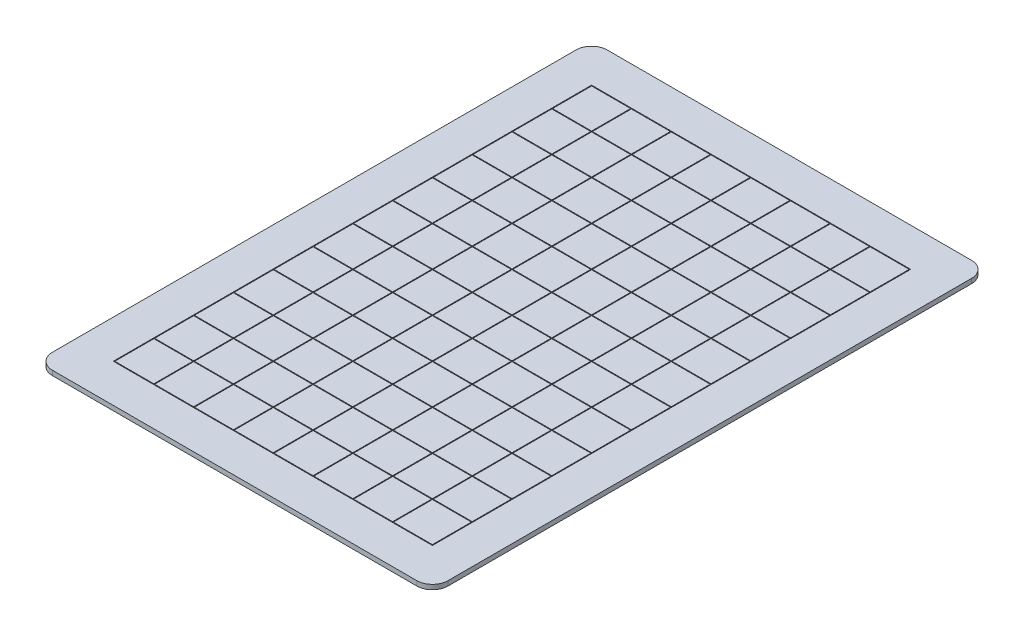
SolidWorks part; units mm, degrees
ref_plane "Front Plane" through (0, 0, 0) normal (0, 0, 1) x (1, 0, 0)
ref_plane "Top Plane" through (0, 0, 0) normal (0, 1, 0) x (1, 0, 0)
ref_plane "Right Plane" through (0, 0, 0) normal (1, 0, 0) x (0, 0, -1)
sketch "Sketch1" plane through (0, 0, 0) normal (0, 1, 0) x (1, 0, 0)
  line L1 (0, 0) -> (253.5, 0)
  line L2 (0, 0) -> (0, 355.5)
  line L3 (0, 355.5) -> (253.5, 355.5)
  line L4 (253.5, 0) -> (253.5, 355.5)
  dimension "D1" = 253.5
  dimension "D2" = 355.5
extrude "Boss-Extrude1" add sketch "Sketch1" along normal blind 3
sketch "Sketch2" plane through (0, 3, 0) normal (0, 1, 0) x (1, 0, 0)
  line L0 (0, 0) -> (253.5, 0) construction
  line L1 (25, 50) -> (50, 50)
  line L2 (25, 50) -> (25, 25)
  line L3 (25, 25) -> (50, 25)
  line L4 (50, 50) -> (50, 25)
  line L5 (0, 355.5) -> (0, 0) construction
  line L6 (50.5, 50) -> (50.5, 25)
  line L7 (50.5, 50) -> (75.5, 50)
  line L8 (75.5, 50) -> (75.5, 25)
  line L9 (50.5, 25) -> (75.5, 25)
  line L10 (76, 50) -> (76, 25)
  line L11 (76, 50) -> (101, 50)
  line L12 (101, 50) -> (101, 25)
  line L13 (76, 25) -> (101, 25)
  line L14 (101.5, 50) -> (101.5, 25)
  line L15 (101.5, 50) -> (126.5, 50)
  line L16 (126.5, 50) -> (126.5, 25)
  line L17 (101.5, 25) -> (126.5, 25)
  line L18 (127, 50) -> (127, 25)
  line L19 (127, 50) -> (152, 50)
  line L20 (152, 50) -> (152, 25)
  line L21 (127, 25) -> (152, 25)
  line L22 (152.5, 50) -> (152.5, 25)
  line L23 (152.5, 50) -> (177.5, 50)
  line L24 (177.5, 50) -> (177.5, 25)
  line L25 (152.5, 25) -> (177.5, 25)
  line L26 (178, 50) -> (178, 25)
  line L27 (178, 50) -> (203, 50)
  line L28 (203, 50) -> (203, 25)
  line L29 (178, 25) -> (203, 25)
  line L30 (203.5, 50) -> (203.5, 25)
  line L31 (203.5, 50) -> (228.5, 50)
  line L32 (228.5, 50) -> (228.5, 25)
  line L33 (203.5, 25) -> (228.5, 25)
  line L34 (50.5, 75.5) -> (50.5, 50.5)
  line L35 (50.5, 75.5) -> (75.5, 75.5)
  line L36 (75.5, 75.5) -> (75.5, 50.5)
  line L37 (50.5, 50.5) -> (75.5, 50.5)
  line L38 (76, 75.5) -> (76, 50.5)
  line L39 (76, 75.5) -> (101, 75.5)
  line L40 (101, 75.5) -> (101, 50.5)
  line L41 (76, 50.5) -> (101, 50.5)
  line L42 (101.5, 75.5) -> (101.5, 50.5)
  line L43 (101.5, 75.5) -> (126.5, 75.5)
  line L44 (126.5, 75.5) -> (126.5, 50.5)
  line L45 (101.5, 50.5) -> (126.5, 50.5)
  line L46 (127, 75.5) -> (127, 50.5)
  line L47 (127, 75.5) -> (152, 75.5)
  line L48 (152, 75.5) -> (152, 50.5)
  line L49 (127, 50.5) -> (152, 50.5)
  line L50 (152.5, 75.5) -> (152.5, 50.5)
  line L51 (152.5, 75.5) -> (177.5, 75.5)
  line L52 (177.5, 75.5) -> (177.5, 50.5)
  line L53 (152.5, 50.5) -> (177.5, 50.5)
  line L54 (178, 75.5) -> (178, 50.5)
  line L55 (178, 75.5) -> (203, 75.5)
  line L56 (203, 75.5) -> (203, 50.5)
  line L57 (178, 50.5) -> (203, 50.5)
  line L58 (203.5, 75.5) -> (203.5, 50.5)
  line L59 (203.5, 75.5) -> (228.5, 75.5)
  line L60 (228.5, 75.5) -> (228.5, 50.5)
  line L61 (203.5, 50.5) -> (228.5, 50.5)
  line L62 (50.5, 101) -> (50.5, 76)
  line L63 (50.5, 101) -> (75.5, 101)
  line L64 (75.5, 101) -> (75.5, 76)
  line L65 (50.5, 76) -> (75.5, 76)
  line L66 (76, 101) -> (76, 76)
  line L67 (76, 101) -> (101, 101)
  line L68 (101, 101) -> (101, 76)
  line L69 (76, 76) -> (101, 76)
  line L70 (101.5, 101) -> (101.5, 76)
  line L71 (101.5, 101) -> (126.5, 101)
  line L72 (126.5, 101) -> (126.5, 76)
  line L73 (101.5, 76) -> (126.5, 76)
  line L74 (127, 101) -> (127, 76)
  line L75 (127, 101) -> (152, 101)
  line L76 (152, 101) -> (152, 76)
  line L77 (127, 76) -> (152, 76)
  line L78 (152.5, 101) -> (152.5, 76)
  line L79 (152.5, 101) -> (177.5, 101)
  line L80 (177.5, 101) -> (177.5, 76)
  line L81 (152.5, 76) -> (177.5, 76)
  line L82 (178, 101) -> (178, 76)
  line L83 (178, 101) -> (203, 101)
  line L84 (203, 101) -> (203, 76)
  line L85 (178, 76) -> (203, 76)
  line L86 (203.5, 101) -> (203.5, 76)
  line L87 (203.5, 101) -> (228.5, 101)
  line L88 (228.5, 101) -> (228.5, 76)
  line L89 (203.5, 76) -> (228.5, 76)
  line L90 (50.5, 126.5) -> (50.5, 101.5)
  line L91 (50.5, 126.5) -> (75.5, 126.5)
  line L92 (75.5, 126.5) -> (75.5, 101.5)
  line L93 (50.5, 101.5) -> (75.5, 101.5)
  line L94 (76, 126.5) -> (76, 101.5)
  line L95 (76, 126.5) -> (101, 126.5)
  line L96 (101, 126.5) -> (101, 101.5)
  line L97 (76, 101.5) -> (101, 101.5)
  line L98 (101.5, 126.5) -> (101.5, 101.5)
  line L99 (101.5, 126.5) -> (126.5, 126.5)
  line L100 (126.5, 126.5) -> (126.5, 101.5)
  line L101 (101.5, 101.5) -> (126.5, 101.5)
  line L102 (127, 126.5) -> (127, 101.5)
  line L103 (127, 126.5) -> (152, 126.5)
  line L104 (152, 126.5) -> (152, 101.5)
  line L105 (127, 101.5) -> (152, 101.5)
  line L106 (152.5, 126.5) -> (152.5, 101.5)
  line L107 (152.5, 126.5) -> (177.5, 126.5)
  line L108 (177.5, 126.5) -> (177.5, 101.5)
  line L109 (152.5, 101.5) -> (177.5, 101.5)
  line L110 (178, 126.5) -> (178, 101.5)
  line L111 (178, 126.5) -> (203, 126.5)
  line L112 (203, 126.5) -> (203, 101.5)
  line L113 (178, 101.5) -> (203, 101.5)
  line L114 (203.5, 126.5) -> (203.5, 101.5)
  line L115 (203.5, 126.5) -> (228.5, 126.5)
  line L116 (228.5, 126.5) -> (228.5, 101.5)
  line L117 (203.5, 101.5) -> (228.5, 101.5)
  line L118 (50.5, 152) -> (50.5, 127)
  line L119 (50.5, 152) -> (75.5, 152)
  line L120 (75.5, 152) -> (75.5, 127)
  line L121 (50.5, 127) -> (75.5, 127)
  line L122 (76, 152) -> (76, 127)
  line L123 (76, 152) -> (101, 152)
  line L124 (101, 152) -> (101, 127)
  line L125 (76, 127) -> (101, 127)
  line L126 (101.5, 152) -> (101.5, 127)
  line L127 (101.5, 152) -> (126.5, 152)
  line L128 (126.5, 152) -> (126.5, 127)
  line L129 (101.5, 127) -> (126.5, 127)
  line L130 (127, 152) -> (127, 127)
  line L131 (127, 152) -> (152, 152)
  line L132 (152, 152) -> (152, 127)
  line L133 (127, 127) -> (152, 127)
  line L134 (152.5, 152) -> (152.5, 127)
  line L135 (152.5, 152) -> (177.5, 152)
  line L136 (177.5, 152) -> (177.5, 127)
  line L137 (152.5, 127) -> (177.5, 127)
  line L138 (178, 152) -> (178, 127)
  line L139 (178, 152) -> (203, 152)
  line L140 (203, 152) -> (203, 127)
  line L141 (178, 127) -> (203, 127)
  line L142 (203.5, 152) -> (203.5, 127)
  line L143 (203.5, 152) -> (228.5, 152)
  line L144 (228.5, 152) -> (228.5, 127)
  line L145 (203.5, 127) -> (228.5, 127)
  line L146 (50.5, 177.5) -> (50.5, 152.5)
  line L147 (50.5, 177.5) -> (75.5, 177.5)
  line L148 (75.5, 177.5) -> (75.5, 152.5)
  line L149 (50.5, 152.5) -> (75.5, 152.5)
  line L150 (76, 177.5) -> (76, 152.5)
  line L151 (76, 177.5) -> (101, 177.5)
  line L152 (101, 177.5) -> (101, 152.5)
  line L153 (76, 152.5) -> (101, 152.5)
  line L154 (101.5, 177.5) -> (101.5, 152.5)
  line L155 (101.5, 177.5) -> (126.5, 177.5)
  line L156 (126.5, 177.5) -> (126.5, 152.5)
  line L157 (101.5, 152.5) -> (126.5, 152.5)
  line L158 (127, 177.5) -> (127, 152.5)
  line L159 (127, 177.5) -> (152, 177.5)
  line L160 (152, 177.5) -> (152, 152.5)
  line L161 (127, 152.5) -> (152, 152.5)
  line L162 (152.5, 177.5) -> (152.5, 152.5)
  line L163 (152.5, 177.5) -> (177.5, 177.5)
  line L164 (177.5, 177.5) -> (177.5, 152.5)
  line L165 (152.5, 152.5) -> (177.5, 152.5)
  line L166 (178, 177.5) -> (178, 152.5)
  line L167 (178, 177.5) -> (203, 177.5)
  line L168 (203, 177.5) -> (203, 152.5)
  line L169 (178, 152.5) -> (203, 152.5)
  line L170 (203.5, 177.5) -> (203.5, 152.5)
  line L171 (203.5, 177.5) -> (228.5, 177.5)
  line L172 (228.5, 177.5) -> (228.5, 152.5)
  line L173 (203.5, 152.5) -> (228.5, 152.5)
  line L174 (50.5, 203) -> (50.5, 178)
  line L175 (50.5, 203) -> (75.5, 203)
  line L176 (75.5, 203) -> (75.5, 178)
  line L177 (50.5, 178) -> (75.5, 178)
  line L178 (76, 203) -> (76, 178)
  line L179 (76, 203) -> (101, 203)
  line L180 (101, 203) -> (101, 178)
  line L181 (76, 178) -> (101, 178)
  line L182 (101.5, 203) -> (101.5, 178)
  line L183 (101.5, 203) -> (126.5, 203)
  line L184 (126.5, 203) -> (126.5, 178)
  line L185 (101.5, 178) -> (126.5, 178)
  line L186 (127, 203) -> (127, 178)
  line L187 (127, 203) -> (152, 203)
  line L188 (152, 203) -> (152, 178)
  line L189 (127, 178) -> (152, 178)
  line L190 (152.5, 203) -> (152.5, 178)
  line L191 (152.5, 203) -> (177.5, 203)
  line L192 (177.5, 203) -> (177.5, 178)
  line L193 (152.5, 178) -> (177.5, 178)
  line L194 (178, 203) -> (178, 178)
  line L195 (178, 203) -> (203, 203)
  line L196 (203, 203) -> (203, 178)
  line L197 (178, 178) -> (203, 178)
  line L198 (203.5, 203) -> (203.5, 178)
  line L199 (203.5, 203) -> (228.5, 203)
  line L200 (228.5, 203) -> (228.5, 178)
  line L201 (203.5, 178) -> (228.5, 178)
  line L202 (50.5, 228.5) -> (50.5, 203.5)
  line L203 (50.5, 228.5) -> (75.5, 228.5)
  line L204 (75.5, 228.5) -> (75.5, 203.5)
  line L205 (50.5, 203.5) -> (75.5, 203.5)
  line L206 (76, 228.5) -> (76, 203.5)
  line L207 (76, 228.5) -> (101, 228.5)
  line L208 (101, 228.5) -> (101, 203.5)
  line L209 (76, 203.5) -> (101, 203.5)
  line L210 (101.5, 228.5) -> (101.5, 203.5)
  line L211 (101.5, 228.5) -> (126.5, 228.5)
  line L212 (126.5, 228.5) -> (126.5, 203.5)
  line L213 (101.5, 203.5) -> (126.5, 203.5)
  line L214 (127, 228.5) -> (127, 203.5)
  line L215 (127, 228.5) -> (152, 228.5)
  line L216 (152, 228.5) -> (152, 203.5)
  line L217 (127, 203.5) -> (152, 203.5)
  line L218 (152.5, 228.5) -> (152.5, 203.5)
  line L219 (152.5, 228.5) -> (177.5, 228.5)
  line L220 (177.5, 228.5) -> (177.5, 203.5)
  line L221 (152.5, 203.5) -> (177.5, 203.5)
  line L222 (178, 228.5) -> (178, 203.5)
  line L223 (178, 228.5) -> (203, 228.5)
  line L224 (203, 228.5) -> (203, 203.5)
  line L225 (178, 203.5) -> (203, 203.5)
  line L226 (203.5, 228.5) -> (203.5, 203.5)
  line L227 (203.5, 228.5) -> (228.5, 228.5)
  line L228 (228.5, 228.5) -> (228.5, 203.5)
  line L229 (203.5, 203.5) -> (228.5, 203.5)
  line L230 (50.5, 254) -> (50.5, 229)
  line L231 (50.5, 254) -> (75.5, 254)
  line L232 (75.5, 254) -> (75.5, 229)
  line L233 (50.5, 229) -> (75.5, 229)
  line L234 (76, 254) -> (76, 229)
  line L235 (76, 254) -> (101, 254)
  line L236 (101, 254) -> (101, 229)
  line L237 (76, 229) -> (101, 229)
  line L238 (101.5, 254) -> (101.5, 229)
  line L239 (101.5, 254) -> (126.5, 254)
  line L240 (126.5, 254) -> (126.5, 229)
  line L241 (101.5, 229) -> (126.5, 229)
  line L242 (127, 254) -> (127, 229)
  line L243 (127, 254) -> (152, 254)
  line L244 (152, 254) -> (152, 229)
  line L245 (127, 229) -> (152, 229)
  line L246 (152.5, 254) -> (152.5, 229)
  line L247 (152.5, 254) -> (177.5, 254)
  line L248 (177.5, 254) -> (177.5, 229)
  line L249 (152.5, 229) -> (177.5, 229)
  line L250 (178, 254) -> (178, 229)
  line L251 (178, 254) -> (203, 254)
  line L252 (203, 254) -> (203, 229)
  line L253 (178, 229) -> (203, 229)
  line L254 (203.5, 254) -> (203.5, 229)
  line L255 (203.5, 254) -> (228.5, 254)
  line L256 (228.5, 254) -> (228.5, 229)
  line L257 (203.5, 229) -> (228.5, 229)
  line L258 (50.5, 279.5) -> (50.5, 254.5)
  line L259 (50.5, 279.5) -> (75.5, 279.5)
  line L260 (75.5, 279.5) -> (75.5, 254.5)
  line L261 (50.5, 254.5) -> (75.5, 254.5)
  line L262 (76, 279.5) -> (76, 254.5)
  line L263 (76, 279.5) -> (101, 279.5)
  line L264 (101, 279.5) -> (101, 254.5)
  line L265 (76, 254.5) -> (101, 254.5)
  line L266 (101.5, 279.5) -> (101.5, 254.5)
  line L267 (101.5, 279.5) -> (126.5, 279.5)
  line L268 (126.5, 279.5) -> (126.5, 254.5)
  line L269 (101.5, 254.5) -> (126.5, 254.5)
  line L270 (127, 279.5) -> (127, 254.5)
  line L271 (127, 279.5) -> (152, 279.5)
  line L272 (152, 279.5) -> (152, 254.5)
  line L273 (127, 254.5) -> (152, 254.5)
  line L274 (152.5, 279.5) -> (152.5, 254.5)
  line L275 (152.5, 279.5) -> (177.5, 279.5)
  line L276 (177.5, 279.5) -> (177.5, 254.5)
  line L277 (152.5, 254.5) -> (177.5, 254.5)
  line L278 (178, 279.5) -> (178, 254.5)
  line L279 (178, 279.5) -> (203, 279.5)
  line L280 (203, 279.5) -> (203, 254.5)
  line L281 (178, 254.5) -> (203, 254.5)
  line L282 (203.5, 279.5) -> (203.5, 254.5)
  line L283 (203.5, 279.5) -> (228.5, 279.5)
  line L284 (228.5, 279.5) -> (228.5, 254.5)
  line L285 (203.5, 254.5) -> (228.5, 254.5)
  line L286 (50.5, 305) -> (50.5, 280)
  line L287 (50.5, 305) -> (75.5, 305)
  line L288 (75.5, 305) -> (75.5, 280)
  line L289 (50.5, 280) -> (75.5, 280)
  line L290 (76, 305) -> (76, 280)
  line L291 (76, 305) -> (101, 305)
  line L292 (101, 305) -> (101, 280)
  line L293 (76, 280) -> (101, 280)
  line L294 (101.5, 305) -> (101.5, 280)
  line L295 (101.5, 305) -> (126.5, 305)
  line L296 (126.5, 305) -> (126.5, 280)
  line L297 (101.5, 280) -> (126.5, 280)
  line L298 (127, 305) -> (127, 280)
  line L299 (127, 305) -> (152, 305)
  line L300 (152, 305) -> (152, 280)
  line L301 (127, 280) -> (152, 280)
  line L302 (152.5, 305) -> (152.5, 280)
  line L303 (152.5, 305) -> (177.5, 305)
  line L304 (177.5, 305) -> (177.5, 280)
  line L305 (152.5, 280) -> (177.5, 280)
  line L306 (178, 305) -> (178, 280)
  line L307 (178, 305) -> (203, 305)
  line L308 (203, 305) -> (203, 280)
  line L309 (178, 280) -> (203, 280)
  line L310 (203.5, 305) -> (203.5, 280)
  line L311 (203.5, 305) -> (228.5, 305)
  line L312 (228.5, 305) -> (228.5, 280)
  line L313 (203.5, 280) -> (228.5, 280)
  line L314 (50.5, 330.5) -> (50.5, 305.5)
  line L315 (50.5, 330.5) -> (75.5, 330.5)
  line L316 (75.5, 330.5) -> (75.5, 305.5)
  line L317 (50.5, 305.5) -> (75.5, 305.5)
  line L318 (76, 330.5) -> (76, 305.5)
  line L319 (76, 330.5) -> (101, 330.5)
  line L320 (101, 330.5) -> (101, 305.5)
  line L321 (76, 305.5) -> (101, 305.5)
  line L322 (101.5, 330.5) -> (101.5, 305.5)
  line L323 (101.5, 330.5) -> (126.5, 330.5)
  line L324 (126.5, 330.5) -> (126.5, 305.5)
  line L325 (101.5, 305.5) -> (126.5, 305.5)
  line L326 (127, 330.5) -> (127, 305.5)
  line L327 (127, 330.5) -> (152, 330.5)
  line L328 (152, 330.5) -> (152, 305.5)
  line L329 (127, 305.5) -> (152, 305.5)
  line L330 (152.5, 330.5) -> (152.5, 305.5)
  line L331 (152.5, 330.5) -> (177.5, 330.5)
  line L332 (177.5, 330.5) -> (177.5, 305.5)
  line L333 (152.5, 305.5) -> (177.5, 305.5)
  line L334 (178, 330.5) -> (178, 305.5)
  line L335 (178, 330.5) -> (203, 330.5)
  line L336 (203, 330.5) -> (203, 305.5)
  line L337 (178, 305.5) -> (203, 305.5)
  line L338 (203.5, 330.5) -> (203.5, 305.5)
  line L339 (203.5, 330.5) -> (228.5, 330.5)
  line L340 (228.5, 330.5) -> (228.5, 305.5)
  line L341 (203.5, 305.5) -> (228.5, 305.5)
  line L342 (25, 75.5) -> (25, 50.5)
  line L343 (25, 75.5) -> (50, 75.5)
  line L344 (50, 75.5) -> (50, 50.5)
  line L345 (25, 50.5) -> (50, 50.5)
  line L346 (25, 101) -> (25, 76)
  line L347 (25, 101) -> (50, 101)
  line L348 (50, 101) -> (50, 76)
  line L349 (25, 76) -> (50, 76)
  line L350 (25, 126.5) -> (25, 101.5)
  line L351 (25, 126.5) -> (50, 126.5)
  line L352 (50, 126.5) -> (50, 101.5)
  line L353 (25, 101.5) -> (50, 101.5)
  line L354 (25, 152) -> (25, 127)
  line L355 (25, 152) -> (50, 152)
  line L356 (50, 152) -> (50, 127)
  line L357 (25, 127) -> (50, 127)
  line L358 (25, 177.5) -> (25, 152.5)
  line L359 (25, 177.5) -> (50, 177.5)
  line L360 (50, 177.5) -> (50, 152.5)
  line L361 (25, 152.5) -> (50, 152.5)
  line L362 (25, 203) -> (25, 178)
  line L363 (25, 203) -> (50, 203)
  line L364 (50, 203) -> (50, 178)
  line L365 (25, 178) -> (50, 178)
  line L366 (25, 228.5) -> (25, 203.5)
  line L367 (25, 228.5) -> (50, 228.5)
  line L368 (50, 228.5) -> (50, 203.5)
  line L369 (25, 203.5) -> (50, 203.5)
  line L370 (25, 254) -> (25, 229)
  line L371 (25, 254) -> (50, 254)
  line L372 (50, 254) -> (50, 229)
  line L373 (25, 229) -> (50, 229)
  line L374 (25, 279.5) -> (25, 254.5)
  line L375 (25, 279.5) -> (50, 279.5)
  line L376 (50, 279.5) -> (50, 254.5)
  line L377 (25, 254.5) -> (50, 254.5)
  line L378 (25, 305) -> (25, 280)
  line L379 (25, 305) -> (50, 305)
  line L380 (50, 305) -> (50, 280)
  line L381 (25, 280) -> (50, 280)
  line L382 (25, 330.5) -> (25, 305.5)
  line L383 (25, 330.5) -> (50, 330.5)
  line L384 (50, 330.5) -> (50, 305.5)
  line L385 (25, 305.5) -> (50, 305.5)
  line L387 (24.5, 331) -> (229, 331)
  line L388 (24.5, 331) -> (24.5, 24.5)
  line L389 (24.5, 24.5) -> (229, 24.5)
  line L390 (229, 331) -> (229, 24.5)
  dimension "D1" = 25
  dimension "D2" = 25
  dimension "D3" = 25
  dimension "D4" = 25
  dimension "D7" = 0.5
  dimension "D8" = 0.5
  dimension "D9" = 0.5
  dimension "D10" = 0.5
  dimension "D11" = 0.5
  dimension "D5" = 8
  dimension "D6" = 12
extrude "Cut-Extrude1" cut sketch "Sketch2" against normal blind 0.5
sketch "Sketch4" plane through (0, 0, 0) normal (0, -1, 0) x (1, 0, 0)
  line L0 (0, -355.5) -> (0, 0) construction
  line L1 (0, 0) -> (253.5, 0) construction
  line L2 (253.5, -355.5) -> (0, -355.5) construction
  line L3 (0, 0) -> (253.5, 0)
  line L4 (253.5, -355.5) -> (0, -355.5)
  line L5 (126.75, -355.5) -> (126.75, 0)
  line L6 (253.5, 0) -> (253.5, -355.5) construction
  line L7 (0, -355.5) -> (0, 0) construction
  line L8 (253.5, 0) -> (253.5, -355.5)
  line L9 (0, -355.5) -> (0, 0)
  line L10 (0, -177.75) -> (253.5, -177.75)
  circle A0 centre (6, -6) radius 1.6
  circle A1 centre (6, -91.875) radius 1.6
  circle A2 centre (6, -177.75) radius 1.6
  circle A3 centre (6, -263.625) radius 1.6
  circle A4 centre (6, -349.5) radius 1.6
  circle A5 centre (247.5, -6) radius 1.6
  circle A6 centre (247.5, -91.875) radius 1.6
  circle A7 centre (247.5, -177.75) radius 1.6
  circle A8 centre (247.5, -263.625) radius 1.6
  circle A10 centre (86.5, -349.5) radius 1.6
  circle A11 centre (167, -349.5) radius 1.6
  circle A12 centre (247.5, -349.5) radius 1.6
  circle A13 centre (167, -6) radius 1.6
  circle A14 centre (86.5, -6) radius 1.6
  dimension "D1" = 3.2
  dimension "D2" = 6
  dimension "D3" = 6
  dimension "D5" = 6
  dimension "D7" = 6
  dimension "D4" = 5
  dimension "D6" = 4
extrude "Cut-Extrude2" cut sketch "Sketch4" against normal blind 1.2 contours A14 | A0 | A13 | A5 | A6 | A7 L10 | A7 L10 | A8 | A12 | A11 | A10 | A4 | A3 | L10 A2 | L10 A2 | A1 region at (6, 0, -177.0709) region at (6, 0, -178.4291) region at (247.5, 0, -177.0709) region at (247.5, 0, -178.4291) region at (6, 0, -6) region at (6, 0, -91.875) region at (6, 0, -263.625) region at (6, 0, -349.5) region at (247.5, 0, -6) region at (247.5, 0, -91.875) region at (247.5, 0, -263.625) region at (86.5, 0, -349.5) region at (167, 0, -349.5) region at (247.5, 0, -349.5) region at (167, 0, -6) region at (86.5, 0, -6)
fillet "Fillet1" radius 10 4 edges at (253.5, 1.5, 0) (0, 1.5, 0) (0, 1.5, -355.5) (253.5, 1.5, -355.5)
sketch "Sketch5" plane through (0, 0, 0) normal (0, -1, 0) x (1, 0, 0)
  line L1 (218.5, -265) -> (213.5, -265)
  line L2 (218.5, -265) -> (218.5, -269)
  line L3 (218.5, -269) -> (213.5, -269)
  line L4 (213.5, -265) -> (213.5, -269)
  line L6 (216, -265) -> (216, -269)
  line L9 (203.5, -279.5) -> (203.5, -254.5) construction
  line L10 (228.5, -279.5) -> (203.5, -279.5) construction
  line L11 (216, -271) -> (216, -275.38)
  line L12 (218.5, -271) -> (213.5, -271)
  line L13 (218.5, -271) -> (218.5, -275.38)
  line L14 (218.5, -275.38) -> (213.5, -275.38)
  line L15 (213.5, -271) -> (213.5, -275.38)
  line L16 (193, -265) -> (193, -269)
  line L17 (193, -265) -> (188, -265)
  line L18 (188, -265) -> (188, -269)
  line L19 (193, -269) -> (188, -269)
  line L20 (193, -271) -> (193, -275.38)
  line L21 (193, -271) -> (188, -271)
  line L22 (188, -271) -> (188, -275.38)
  line L23 (193, -275.38) -> (188, -275.38)
  line L24 (167.5, -265) -> (167.5, -269)
  line L25 (167.5, -265) -> (162.5, -265)
  line L26 (162.5, -265) -> (162.5, -269)
  line L27 (167.5, -269) -> (162.5, -269)
  line L28 (167.5, -271) -> (167.5, -275.38)
  line L29 (167.5, -271) -> (162.5, -271)
  line L30 (162.5, -271) -> (162.5, -275.38)
  line L31 (167.5, -275.38) -> (162.5, -275.38)
  line L32 (142, -265) -> (142, -269)
  line L33 (142, -265) -> (137, -265)
  line L34 (137, -265) -> (137, -269)
  line L35 (142, -269) -> (137, -269)
  line L36 (142, -271) -> (142, -275.38)
  line L37 (142, -271) -> (137, -271)
  line L38 (137, -271) -> (137, -275.38)
  line L39 (142, -275.38) -> (137, -275.38)
  line L40 (116.5, -265) -> (116.5, -269)
  line L41 (116.5, -265) -> (111.5, -265)
  line L42 (111.5, -265) -> (111.5, -269)
  line L43 (116.5, -269) -> (111.5, -269)
  line L44 (116.5, -271) -> (116.5, -275.38)
  line L45 (116.5, -271) -> (111.5, -271)
  line L46 (111.5, -271) -> (111.5, -275.38)
  line L47 (116.5, -275.38) -> (111.5, -275.38)
  line L48 (91, -265) -> (91, -269)
  line L49 (91, -265) -> (86, -265)
  line L50 (86, -265) -> (86, -269)
  line L51 (91, -269) -> (86, -269)
  line L52 (91, -271) -> (91, -275.38)
  line L53 (91, -271) -> (86, -271)
  line L54 (86, -271) -> (86, -275.38)
  line L55 (91, -275.38) -> (86, -275.38)
  line L56 (65.5, -265) -> (65.5, -269)
  line L57 (65.5, -265) -> (60.5, -265)
  line L58 (60.5, -265) -> (60.5, -269)
  line L59 (65.5, -269) -> (60.5, -269)
  line L60 (65.5, -271) -> (65.5, -275.38)
  line L61 (65.5, -271) -> (60.5, -271)
  line L62 (60.5, -271) -> (60.5, -275.38)
  line L63 (65.5, -275.38) -> (60.5, -275.38)
  line L64 (40, -265) -> (40, -269)
  line L65 (40, -265) -> (35, -265)
  line L66 (35, -265) -> (35, -269)
  line L67 (40, -269) -> (35, -269)
  line L68 (40, -271) -> (40, -275.38)
  line L69 (40, -271) -> (35, -271)
  line L70 (35, -271) -> (35, -275.38)
  line L71 (40, -275.38) -> (35, -275.38)
  line L72 (193, -239.5) -> (193, -243.5)
  line L73 (193, -239.5) -> (188, -239.5)
  line L74 (188, -239.5) -> (188, -243.5)
  line L75 (193, -243.5) -> (188, -243.5)
  line L76 (193, -245.5) -> (193, -249.88)
  line L77 (193, -245.5) -> (188, -245.5)
  line L78 (188, -245.5) -> (188, -249.88)
  line L79 (193, -249.88) -> (188, -249.88)
  line L80 (167.5, -239.5) -> (167.5, -243.5)
  line L81 (167.5, -239.5) -> (162.5, -239.5)
  line L82 (162.5, -239.5) -> (162.5, -243.5)
  line L83 (167.5, -243.5) -> (162.5, -243.5)
  line L84 (167.5, -245.5) -> (167.5, -249.88)
  line L85 (167.5, -245.5) -> (162.5, -245.5)
  line L86 (162.5, -245.5) -> (162.5, -249.88)
  line L87 (167.5, -249.88) -> (162.5, -249.88)
  line L88 (142, -239.5) -> (142, -243.5)
  line L89 (142, -239.5) -> (137, -239.5)
  line L90 (137, -239.5) -> (137, -243.5)
  line L91 (142, -243.5) -> (137, -243.5)
  line L92 (142, -245.5) -> (142, -249.88)
  line L93 (142, -245.5) -> (137, -245.5)
  line L94 (137, -245.5) -> (137, -249.88)
  line L95 (142, -249.88) -> (137, -249.88)
  line L96 (116.5, -239.5) -> (116.5, -243.5)
  line L97 (116.5, -239.5) -> (111.5, -239.5)
  line L98 (111.5, -239.5) -> (111.5, -243.5)
  line L99 (116.5, -243.5) -> (111.5, -243.5)
  line L100 (116.5, -245.5) -> (116.5, -249.88)
  line L101 (116.5, -245.5) -> (111.5, -245.5)
  line L102 (111.5, -245.5) -> (111.5, -249.88)
  line L103 (116.5, -249.88) -> (111.5, -249.88)
  line L104 (91, -239.5) -> (91, -243.5)
  line L105 (91, -239.5) -> (86, -239.5)
  line L106 (86, -239.5) -> (86, -243.5)
  line L107 (91, -243.5) -> (86, -243.5)
  line L108 (91, -245.5) -> (91, -249.88)
  line L109 (91, -245.5) -> (86, -245.5)
  line L110 (86, -245.5) -> (86, -249.88)
  line L111 (91, -249.88) -> (86, -249.88)
  line L112 (65.5, -239.5) -> (65.5, -243.5)
  line L113 (65.5, -239.5) -> (60.5, -239.5)
  line L114 (60.5, -239.5) -> (60.5, -243.5)
  line L115 (65.5, -243.5) -> (60.5, -243.5)
  line L116 (65.5, -245.5) -> (65.5, -249.88)
  line L117 (65.5, -245.5) -> (60.5, -245.5)
  line L118 (60.5, -245.5) -> (60.5, -249.88)
  line L119 (65.5, -249.88) -> (60.5, -249.88)
  line L120 (40, -239.5) -> (40, -243.5)
  line L121 (40, -239.5) -> (35, -239.5)
  line L122 (35, -239.5) -> (35, -243.5)
  line L123 (40, -243.5) -> (35, -243.5)
  line L124 (40, -245.5) -> (40, -249.88)
  line L125 (40, -245.5) -> (35, -245.5)
  line L126 (35, -245.5) -> (35, -249.88)
  line L127 (40, -249.88) -> (35, -249.88)
  line L128 (193, -214) -> (193, -218)
  line L129 (193, -214) -> (188, -214)
  line L130 (188, -214) -> (188, -218)
  line L131 (193, -218) -> (188, -218)
  line L132 (193, -220) -> (193, -224.38)
  line L133 (193, -220) -> (188, -220)
  line L134 (188, -220) -> (188, -224.38)
  line L135 (193, -224.38) -> (188, -224.38)
  line L136 (167.5, -214) -> (167.5, -218)
  line L137 (167.5, -214) -> (162.5, -214)
  line L138 (162.5, -214) -> (162.5, -218)
  line L139 (167.5, -218) -> (162.5, -218)
  line L140 (167.5, -220) -> (167.5, -224.38)
  line L141 (167.5, -220) -> (162.5, -220)
  line L142 (162.5, -220) -> (162.5, -224.38)
  line L143 (167.5, -224.38) -> (162.5, -224.38)
  line L144 (142, -214) -> (142, -218)
  line L145 (142, -214) -> (137, -214)
  line L146 (137, -214) -> (137, -218)
  line L147 (142, -218) -> (137, -218)
  line L148 (142, -220) -> (142, -224.38)
  line L149 (142, -220) -> (137, -220)
  line L150 (137, -220) -> (137, -224.38)
  line L151 (142, -224.38) -> (137, -224.38)
  line L152 (116.5, -214) -> (116.5, -218)
  line L153 (116.5, -214) -> (111.5, -214)
  line L154 (111.5, -214) -> (111.5, -218)
  line L155 (116.5, -218) -> (111.5, -218)
  line L156 (116.5, -220) -> (116.5, -224.38)
  line L157 (116.5, -220) -> (111.5, -220)
  line L158 (111.5, -220) -> (111.5, -224.38)
  line L159 (116.5, -224.38) -> (111.5, -224.38)
  line L160 (91, -214) -> (91, -218)
  line L161 (91, -214) -> (86, -214)
  line L162 (86, -214) -> (86, -218)
  line L163 (91, -218) -> (86, -218)
  line L164 (91, -220) -> (91, -224.38)
  line L165 (91, -220) -> (86, -220)
  line L166 (86, -220) -> (86, -224.38)
  line L167 (91, -224.38) -> (86, -224.38)
  line L168 (65.5, -214) -> (65.5, -218)
  line L169 (65.5, -214) -> (60.5, -214)
  line L170 (60.5, -214) -> (60.5, -218)
  line L171 (65.5, -218) -> (60.5, -218)
  line L172 (65.5, -220) -> (65.5, -224.38)
  line L173 (65.5, -220) -> (60.5, -220)
  line L174 (60.5, -220) -> (60.5, -224.38)
  line L175 (65.5, -224.38) -> (60.5, -224.38)
  line L176 (40, -214) -> (40, -218)
  line L177 (40, -214) -> (35, -214)
  line L178 (35, -214) -> (35, -218)
  line L179 (40, -218) -> (35, -218)
  line L180 (40, -220) -> (40, -224.38)
  line L181 (40, -220) -> (35, -220)
  line L182 (35, -220) -> (35, -224.38)
  line L183 (40, -224.38) -> (35, -224.38)
  line L184 (193, -188.5) -> (193, -192.5)
  line L185 (193, -188.5) -> (188, -188.5)
  line L186 (188, -188.5) -> (188, -192.5)
  line L187 (193, -192.5) -> (188, -192.5)
  line L188 (193, -194.5) -> (193, -198.88)
  line L189 (193, -194.5) -> (188, -194.5)
  line L190 (188, -194.5) -> (188, -198.88)
  line L191 (193, -198.88) -> (188, -198.88)
  line L192 (167.5, -188.5) -> (167.5, -192.5)
  line L193 (167.5, -188.5) -> (162.5, -188.5)
  line L194 (162.5, -188.5) -> (162.5, -192.5)
  line L195 (167.5, -192.5) -> (162.5, -192.5)
  line L196 (167.5, -194.5) -> (167.5, -198.88)
  line L197 (167.5, -194.5) -> (162.5, -194.5)
  line L198 (162.5, -194.5) -> (162.5, -198.88)
  line L199 (167.5, -198.88) -> (162.5, -198.88)
  line L200 (142, -188.5) -> (142, -192.5)
  line L201 (142, -188.5) -> (137, -188.5)
  line L202 (137, -188.5) -> (137, -192.5)
  line L203 (142, -192.5) -> (137, -192.5)
  line L204 (142, -194.5) -> (142, -198.88)
  line L205 (142, -194.5) -> (137, -194.5)
  line L206 (137, -194.5) -> (137, -198.88)
  line L207 (142, -198.88) -> (137, -198.88)
  line L208 (116.5, -188.5) -> (116.5, -192.5)
  line L209 (116.5, -188.5) -> (111.5, -188.5)
  line L210 (111.5, -188.5) -> (111.5, -192.5)
  line L211 (116.5, -192.5) -> (111.5, -192.5)
  line L212 (116.5, -194.5) -> (116.5, -198.88)
  line L213 (116.5, -194.5) -> (111.5, -194.5)
  line L214 (111.5, -194.5) -> (111.5, -198.88)
  line L215 (116.5, -198.88) -> (111.5, -198.88)
  line L216 (91, -188.5) -> (91, -192.5)
  line L217 (91, -188.5) -> (86, -188.5)
  line L218 (86, -188.5) -> (86, -192.5)
  line L219 (91, -192.5) -> (86, -192.5)
  line L220 (91, -194.5) -> (91, -198.88)
  line L221 (91, -194.5) -> (86, -194.5)
  line L222 (86, -194.5) -> (86, -198.88)
  line L223 (91, -198.88) -> (86, -198.88)
  line L224 (65.5, -188.5) -> (65.5, -192.5)
  line L225 (65.5, -188.5) -> (60.5, -188.5)
  line L226 (60.5, -188.5) -> (60.5, -192.5)
  line L227 (65.5, -192.5) -> (60.5, -192.5)
  line L228 (65.5, -194.5) -> (65.5, -198.88)
  line L229 (65.5, -194.5) -> (60.5, -194.5)
  line L230 (60.5, -194.5) -> (60.5, -198.88)
  line L231 (65.5, -198.88) -> (60.5, -198.88)
  line L232 (40, -188.5) -> (40, -192.5)
  line L233 (40, -188.5) -> (35, -188.5)
  line L234 (35, -188.5) -> (35, -192.5)
  line L235 (40, -192.5) -> (35, -192.5)
  line L236 (40, -194.5) -> (40, -198.88)
  line L237 (40, -194.5) -> (35, -194.5)
  line L238 (35, -194.5) -> (35, -198.88)
  line L239 (40, -198.88) -> (35, -198.88)
  line L240 (193, -163) -> (193, -167)
  line L241 (193, -163) -> (188, -163)
  line L242 (188, -163) -> (188, -167)
  line L243 (193, -167) -> (188, -167)
  line L244 (193, -169) -> (193, -173.38)
  line L245 (193, -169) -> (188, -169)
  line L246 (188, -169) -> (188, -173.38)
  line L247 (193, -173.38) -> (188, -173.38)
  line L248 (167.5, -163) -> (167.5, -167)
  line L249 (167.5, -163) -> (162.5, -163)
  line L250 (162.5, -163) -> (162.5, -167)
  line L251 (167.5, -167) -> (162.5, -167)
  line L252 (167.5, -169) -> (167.5, -173.38)
  line L253 (167.5, -169) -> (162.5, -169)
  line L254 (162.5, -169) -> (162.5, -173.38)
  line L255 (167.5, -173.38) -> (162.5, -173.38)
  line L256 (142, -163) -> (142, -167)
  line L257 (142, -163) -> (137, -163)
  line L258 (137, -163) -> (137, -167)
  line L259 (142, -167) -> (137, -167)
  line L260 (142, -169) -> (142, -173.38)
  line L261 (142, -169) -> (137, -169)
  line L262 (137, -169) -> (137, -173.38)
  line L263 (142, -173.38) -> (137, -173.38)
  line L264 (116.5, -163) -> (116.5, -167)
  line L265 (116.5, -163) -> (111.5, -163)
  line L266 (111.5, -163) -> (111.5, -167)
  line L267 (116.5, -167) -> (111.5, -167)
  line L268 (116.5, -169) -> (116.5, -173.38)
  line L269 (116.5, -169) -> (111.5, -169)
  line L270 (111.5, -169) -> (111.5, -173.38)
  line L271 (116.5, -173.38) -> (111.5, -173.38)
  line L272 (91, -163) -> (91, -167)
  line L273 (91, -163) -> (86, -163)
  line L274 (86, -163) -> (86, -167)
  line L275 (91, -167) -> (86, -167)
  line L276 (91, -169) -> (91, -173.38)
  line L277 (91, -169) -> (86, -169)
  line L278 (86, -169) -> (86, -173.38)
  line L279 (91, -173.38) -> (86, -173.38)
  line L280 (65.5, -163) -> (65.5, -167)
  line L281 (65.5, -163) -> (60.5, -163)
  line L282 (60.5, -163) -> (60.5, -167)
  line L283 (65.5, -167) -> (60.5, -167)
  line L284 (65.5, -169) -> (65.5, -173.38)
  line L285 (65.5, -169) -> (60.5, -169)
  line L286 (60.5, -169) -> (60.5, -173.38)
  line L287 (65.5, -173.38) -> (60.5, -173.38)
  line L288 (40, -163) -> (40, -167)
  line L289 (40, -163) -> (35, -163)
  line L290 (35, -163) -> (35, -167)
  line L291 (40, -167) -> (35, -167)
  line L292 (40, -169) -> (40, -173.38)
  line L293 (40, -169) -> (35, -169)
  line L294 (35, -169) -> (35, -173.38)
  line L295 (40, -173.38) -> (35, -173.38)
  line L296 (193, -137.5) -> (193, -141.5)
  line L297 (193, -137.5) -> (188, -137.5)
  line L298 (188, -137.5) -> (188, -141.5)
  line L299 (193, -141.5) -> (188, -141.5)
  line L300 (193, -143.5) -> (193, -147.88)
  line L301 (193, -143.5) -> (188, -143.5)
  line L302 (188, -143.5) -> (188, -147.88)
  line L303 (193, -147.88) -> (188, -147.88)
  line L304 (167.5, -137.5) -> (167.5, -141.5)
  line L305 (167.5, -137.5) -> (162.5, -137.5)
  line L306 (162.5, -137.5) -> (162.5, -141.5)
  line L307 (167.5, -141.5) -> (162.5, -141.5)
  line L308 (167.5, -143.5) -> (167.5, -147.88)
  line L309 (167.5, -143.5) -> (162.5, -143.5)
  line L310 (162.5, -143.5) -> (162.5, -147.88)
  line L311 (167.5, -147.88) -> (162.5, -147.88)
  line L312 (142, -137.5) -> (142, -141.5)
  line L313 (142, -137.5) -> (137, -137.5)
  line L314 (137, -137.5) -> (137, -141.5)
  line L315 (142, -141.5) -> (137, -141.5)
  line L316 (142, -143.5) -> (142, -147.88)
  line L317 (142, -143.5) -> (137, -143.5)
  line L318 (137, -143.5) -> (137, -147.88)
  line L319 (142, -147.88) -> (137, -147.88)
  line L320 (116.5, -137.5) -> (116.5, -141.5)
  line L321 (116.5, -137.5) -> (111.5, -137.5)
  line L322 (111.5, -137.5) -> (111.5, -141.5)
  line L323 (116.5, -141.5) -> (111.5, -141.5)
  line L324 (116.5, -143.5) -> (116.5, -147.88)
  line L325 (116.5, -143.5) -> (111.5, -143.5)
  line L326 (111.5, -143.5) -> (111.5, -147.88)
  line L327 (116.5, -147.88) -> (111.5, -147.88)
  line L328 (91, -137.5) -> (91, -141.5)
  line L329 (91, -137.5) -> (86, -137.5)
  line L330 (86, -137.5) -> (86, -141.5)
  line L331 (91, -141.5) -> (86, -141.5)
  line L332 (91, -143.5) -> (91, -147.88)
  line L333 (91, -143.5) -> (86, -143.5)
  line L334 (86, -143.5) -> (86, -147.88)
  line L335 (91, -147.88) -> (86, -147.88)
  line L336 (65.5, -137.5) -> (65.5, -141.5)
  line L337 (65.5, -137.5) -> (60.5, -137.5)
  line L338 (60.5, -137.5) -> (60.5, -141.5)
  line L339 (65.5, -141.5) -> (60.5, -141.5)
  line L340 (65.5, -143.5) -> (65.5, -147.88)
  line L341 (65.5, -143.5) -> (60.5, -143.5)
  line L342 (60.5, -143.5) -> (60.5, -147.88)
  line L343 (65.5, -147.88) -> (60.5, -147.88)
  line L344 (40, -137.5) -> (40, -141.5)
  line L345 (40, -137.5) -> (35, -137.5)
  line L346 (35, -137.5) -> (35, -141.5)
  line L347 (40, -141.5) -> (35, -141.5)
  line L348 (40, -143.5) -> (40, -147.88)
  line L349 (40, -143.5) -> (35, -143.5)
  line L350 (35, -143.5) -> (35, -147.88)
  line L351 (40, -147.88) -> (35, -147.88)
  line L352 (193, -112) -> (193, -116)
  line L353 (193, -112) -> (188, -112)
  line L354 (188, -112) -> (188, -116)
  line L355 (193, -116) -> (188, -116)
  line L356 (193, -118) -> (193, -122.38)
  line L357 (193, -118) -> (188, -118)
  line L358 (188, -118) -> (188, -122.38)
  line L359 (193, -122.38) -> (188, -122.38)
  line L360 (167.5, -112) -> (167.5, -116)
  line L361 (167.5, -112) -> (162.5, -112)
  line L362 (162.5, -112) -> (162.5, -116)
  line L363 (167.5, -116) -> (162.5, -116)
  line L364 (167.5, -118) -> (167.5, -122.38)
  line L365 (167.5, -118) -> (162.5, -118)
  line L366 (162.5, -118) -> (162.5, -122.38)
  line L367 (167.5, -122.38) -> (162.5, -122.38)
  line L368 (142, -112) -> (142, -116)
  line L369 (142, -112) -> (137, -112)
  line L370 (137, -112) -> (137, -116)
  line L371 (142, -116) -> (137, -116)
  line L372 (142, -118) -> (142, -122.38)
  line L373 (142, -118) -> (137, -118)
  line L374 (137, -118) -> (137, -122.38)
  line L375 (142, -122.38) -> (137, -122.38)
  line L376 (116.5, -112) -> (116.5, -116)
  line L377 (116.5, -112) -> (111.5, -112)
  line L378 (111.5, -112) -> (111.5, -116)
  line L379 (116.5, -116) -> (111.5, -116)
  line L380 (116.5, -118) -> (116.5, -122.38)
  line L381 (116.5, -118) -> (111.5, -118)
  line L382 (111.5, -118) -> (111.5, -122.38)
  line L383 (116.5, -122.38) -> (111.5, -122.38)
  line L384 (91, -112) -> (91, -116)
  line L385 (91, -112) -> (86, -112)
  line L386 (86, -112) -> (86, -116)
  line L387 (91, -116) -> (86, -116)
  line L388 (91, -118) -> (91, -122.38)
  line L389 (91, -118) -> (86, -118)
  line L390 (86, -118) -> (86, -122.38)
  line L391 (91, -122.38) -> (86, -122.38)
  line L392 (65.5, -112) -> (65.5, -116)
  line L393 (65.5, -112) -> (60.5, -112)
  line L394 (60.5, -112) -> (60.5, -116)
  line L395 (65.5, -116) -> (60.5, -116)
  line L396 (65.5, -118) -> (65.5, -122.38)
  line L397 (65.5, -118) -> (60.5, -118)
  line L398 (60.5, -118) -> (60.5, -122.38)
  line L399 (65.5, -122.38) -> (60.5, -122.38)
  line L400 (40, -112) -> (40, -116)
  line L401 (40, -112) -> (35, -112)
  line L402 (35, -112) -> (35, -116)
  line L403 (40, -116) -> (35, -116)
  line L404 (40, -118) -> (40, -122.38)
  line L405 (40, -118) -> (35, -118)
  line L406 (35, -118) -> (35, -122.38)
  line L407 (40, -122.38) -> (35, -122.38)
  line L408 (193, -86.5) -> (193, -90.5)
  line L409 (193, -86.5) -> (188, -86.5)
  line L410 (188, -86.5) -> (188, -90.5)
  line L411 (193, -90.5) -> (188, -90.5)
  line L412 (193, -92.5) -> (193, -96.88)
  line L413 (193, -92.5) -> (188, -92.5)
  line L414 (188, -92.5) -> (188, -96.88)
  line L415 (193, -96.88) -> (188, -96.88)
  line L416 (167.5, -86.5) -> (167.5, -90.5)
  line L417 (167.5, -86.5) -> (162.5, -86.5)
  line L418 (162.5, -86.5) -> (162.5, -90.5)
  line L419 (167.5, -90.5) -> (162.5, -90.5)
  line L420 (167.5, -92.5) -> (167.5, -96.88)
  line L421 (167.5, -92.5) -> (162.5, -92.5)
  line L422 (162.5, -92.5) -> (162.5, -96.88)
  line L423 (167.5, -96.88) -> (162.5, -96.88)
  line L424 (142, -86.5) -> (142, -90.5)
  line L425 (142, -86.5) -> (137, -86.5)
  line L426 (137, -86.5) -> (137, -90.5)
  line L427 (142, -90.5) -> (137, -90.5)
  line L428 (142, -92.5) -> (142, -96.88)
  line L429 (142, -92.5) -> (137, -92.5)
  line L430 (137, -92.5) -> (137, -96.88)
  line L431 (142, -96.88) -> (137, -96.88)
  line L432 (116.5, -86.5) -> (116.5, -90.5)
  line L433 (116.5, -86.5) -> (111.5, -86.5)
  line L434 (111.5, -86.5) -> (111.5, -90.5)
  line L435 (116.5, -90.5) -> (111.5, -90.5)
  line L436 (116.5, -92.5) -> (116.5, -96.88)
  line L437 (116.5, -92.5) -> (111.5, -92.5)
  line L438 (111.5, -92.5) -> (111.5, -96.88)
  line L439 (116.5, -96.88) -> (111.5, -96.88)
  line L440 (91, -86.5) -> (91, -90.5)
  line L441 (91, -86.5) -> (86, -86.5)
  line L442 (86, -86.5) -> (86, -90.5)
  line L443 (91, -90.5) -> (86, -90.5)
  line L444 (91, -92.5) -> (91, -96.88)
  line L445 (91, -92.5) -> (86, -92.5)
  line L446 (86, -92.5) -> (86, -96.88)
  line L447 (91, -96.88) -> (86, -96.88)
  line L448 (65.5, -86.5) -> (65.5, -90.5)
  line L449 (65.5, -86.5) -> (60.5, -86.5)
  line L450 (60.5, -86.5) -> (60.5, -90.5)
  line L451 (65.5, -90.5) -> (60.5, -90.5)
  line L452 (65.5, -92.5) -> (65.5, -96.88)
  line L453 (65.5, -92.5) -> (60.5, -92.5)
  line L454 (60.5, -92.5) -> (60.5, -96.88)
  line L455 (65.5, -96.88) -> (60.5, -96.88)
  line L456 (40, -86.5) -> (40, -90.5)
  line L457 (40, -86.5) -> (35, -86.5)
  line L458 (35, -86.5) -> (35, -90.5)
  line L459 (40, -90.5) -> (35, -90.5)
  line L460 (40, -92.5) -> (40, -96.88)
  line L461 (40, -92.5) -> (35, -92.5)
  line L462 (35, -92.5) -> (35, -96.88)
  line L463 (40, -96.88) -> (35, -96.88)
  line L464 (218.5, -239.5) -> (218.5, -243.5)
  line L465 (218.5, -239.5) -> (213.5, -239.5)
  line L466 (213.5, -239.5) -> (213.5, -243.5)
  line L467 (218.5, -243.5) -> (213.5, -243.5)
  line L468 (218.5, -245.5) -> (218.5, -249.88)
  line L469 (218.5, -245.5) -> (213.5, -245.5)
  line L470 (213.5, -245.5) -> (213.5, -249.88)
  line L471 (218.5, -249.88) -> (213.5, -249.88)
  line L472 (218.5, -214) -> (218.5, -218)
  line L473 (218.5, -214) -> (213.5, -214)
  line L474 (213.5, -214) -> (213.5, -218)
  line L475 (218.5, -218) -> (213.5, -218)
  line L476 (218.5, -220) -> (218.5, -224.38)
  line L477 (218.5, -220) -> (213.5, -220)
  line L478 (213.5, -220) -> (213.5, -224.38)
  line L479 (218.5, -224.38) -> (213.5, -224.38)
  line L480 (218.5, -188.5) -> (218.5, -192.5)
  line L481 (218.5, -188.5) -> (213.5, -188.5)
  line L482 (213.5, -188.5) -> (213.5, -192.5)
  line L483 (218.5, -192.5) -> (213.5, -192.5)
  line L484 (218.5, -194.5) -> (218.5, -198.88)
  line L485 (218.5, -194.5) -> (213.5, -194.5)
  line L486 (213.5, -194.5) -> (213.5, -198.88)
  line L487 (218.5, -198.88) -> (213.5, -198.88)
  line L488 (218.5, -163) -> (218.5, -167)
  line L489 (218.5, -163) -> (213.5, -163)
  line L490 (213.5, -163) -> (213.5, -167)
  line L491 (218.5, -167) -> (213.5, -167)
  line L492 (218.5, -169) -> (218.5, -173.38)
  line L493 (218.5, -169) -> (213.5, -169)
  line L494 (213.5, -169) -> (213.5, -173.38)
  line L495 (218.5, -173.38) -> (213.5, -173.38)
  line L496 (218.5, -137.5) -> (218.5, -141.5)
  line L497 (218.5, -137.5) -> (213.5, -137.5)
  line L498 (213.5, -137.5) -> (213.5, -141.5)
  line L499 (218.5, -141.5) -> (213.5, -141.5)
  line L500 (218.5, -143.5) -> (218.5, -147.88)
  line L501 (218.5, -143.5) -> (213.5, -143.5)
  line L502 (213.5, -143.5) -> (213.5, -147.88)
  line L503 (218.5, -147.88) -> (213.5, -147.88)
  line L504 (218.5, -112) -> (218.5, -116)
  line L505 (218.5, -112) -> (213.5, -112)
  line L506 (213.5, -112) -> (213.5, -116)
  line L507 (218.5, -116) -> (213.5, -116)
  line L508 (218.5, -118) -> (218.5, -122.38)
  line L509 (218.5, -118) -> (213.5, -118)
  line L510 (213.5, -118) -> (213.5, -122.38)
  line L511 (218.5, -122.38) -> (213.5, -122.38)
  line L512 (218.5, -86.5) -> (218.5, -90.5)
  line L513 (218.5, -86.5) -> (213.5, -86.5)
  line L514 (213.5, -86.5) -> (213.5, -90.5)
  line L515 (218.5, -90.5) -> (213.5, -90.5)
  line L516 (218.5, -92.5) -> (218.5, -96.88)
  line L517 (218.5, -92.5) -> (213.5, -92.5)
  line L518 (213.5, -92.5) -> (213.5, -96.88)
  line L519 (218.5, -96.88) -> (213.5, -96.88)
  point P4 (216, -267)
  dimension "D1" = 5
  dimension "D2" = 4
  dimension "D3" = 12.5
  dimension "D4" = 12.5
  dimension "D5" = 5
  dimension "D6" = 4.38
  dimension "D7" = 0
  dimension "D8" = 2
  dimension "D9" = 8
  dimension "D10" = 8
extrude "Cut-Extrude3" cut sketch "Sketch5" against normal blind 2 contours L415 L412 L413 L414 | L514 L515 L512 L513 | L518 L519 L516 L517 | L410 L411 L408 L409 | L418 L419 L416 L417 | L422 L423 L420 L421 | L426 L427 L424 L425 | L430 L431 L428 L429 | L434 L435 L432 L433 | L438 L439 L436 L437 | L442 L443 L440 L441 | L446 L447 L444 L445 | L450 L451 L448 L449 | L454 L455 L452 L453 | L458 L459 L456 L457 | L462 L463 L460 L461 | L506 L507 L504 L505 | L510 L511 L508 L509 | L354 L355 L352 L353 | L358 L359 L356 L357 | L362 L363 L360 L361 | L366 L367 L364 L365 | L370 L371 L368 L369 | L374 L375 L372 L373 | L378 L379 L376 L377 | L382 L383 L380 L381 | L386 L387 L384 L385 | L390 L391 L388 L389 | L394 L395 L392 L393 | L398 L399 L396 L397 | L402 L403 L400 L401 | L406 L407 L404 L405 | L498 L499 L496 L497 | L502 L503 L500 L501 | L298 L299 L296 L297 | L302 L303 L300 L301 | L306 L307 L304 L305 | L310 L311 L308 L309 | L314 L315 L312 L313 | L318 L319 L316 L317 | L322 L323 L320 L321 | L326 L327 L324 L325 | L330 L331 L328 L329 | L334 L335 L332 L333 | L338 L339 L336 L337 | L342 L343 L340 L341 | L346 L347 L344 L345 | L350 L351 L348 L349 | L490 L491 L488 L489 | L494 L495 L492 L493 | L242 L243 L240 L241 | L246 L247 L244 L245 | L250 L251 L248 L249 | L254 L255 L252 L253 | L258 L259 L256 L257 | L262 L263 L260 L261 | L266 L267 L264 L265 | L270 L271 L268 L269 | L274 L275 L272 L273 | L278 L279 L276 L277 | L282 L283 L280 L281 | L286 L287 L284 L285 | L290 L291 L288 L289 | L294 L295 L292 L293 | L482 L483 L480 L481 | L486 L487 L484 L485 | L185 L186 L187 L184 | L191 L190 L189 L188 | L193 L194 L195 L192 | L199 L198 L197 L196 | L201 L202 L203 L200 | L207 L206 L205 L204 | L209 L210 L211 L208 | L215 L214 L213 L212 | L217 L218 L219 L216 | L223 L222 L221 L220 | L225 L226 L227 L224 | L231 L230 L229 L228 | L233 L234 L235 L232 | L239 L238 L237 L236 | L473 L474 L475 L472 | L479 L478 L477 L476 | L129 L130 L131 L128 | L135 L134 L133 L132 | L137 L138 L139 L136 | L143 L142 L141 L140 | L145 L146 L147 L144 | L151 L150 L149 L148 | L153 L154 L155 L152 | L159 L158 L157 L156 | L161 L162 L163 L160 | L167 L166 L165 L164 | L169 L170 L171 L168 | L175 L174 L173 L172 | L177 L178 L179 L176 | L183 L182 L181 L180 | L465 L466 L467 L464 | L470 L471 L468 L469 | L73 L74 L75 L72 | L79 L78 L77 L76 region at (190.5, 0, -94.69)
extrude "Cut-Extrude4" cut sketch "Sketch5<3>" against normal blind 2 contours L67 L64 L65 L66 | L63 L60 L61 L62 | L59 L56 L57 L58 | L51 L48 L49 L50 | L55 L52 L53 L54 | L123 L120 L121 L122 | L127 L124 L125 L126 | L107 L104 L105 L106 | L111 L108 L109 L110 | L99 L96 L97 L98 | L103 L100 L101 L102 | L43 L40 L41 L42 | L47 L44 L45 L46 | L91 L88 L89 L90 | L95 L92 L93 L94 | L83 L80 L81 L82 | L87 L84 L85 L86 | L35 L32 L33 L34 | L39 L36 L37 L38 | L27 L24 L25 L26 | L31 L28 L29 L30 | L19 L16 L17 L18 | L23 L20 L21 L22 | L6 L1 L4 L3 | L1 L6 L3 L2 | L12 L15 L14 L11 | L14 L13 L12 L11 | L71 L70 L69 L68 | L115 L114 L113 L112 | L119 L118 L117 L116 region at (217.25, 0, -267) region at (214.75, 0, -267) region at (217.25, 0, -273.19) region at (214.75, 0, -273.19) region at (190.5, 0, -267) region at (190.5, 0, -273.19) region at (165, 0, -267) region at (165, 0, -273.19) region at (139.5, 0, -267) region at (139.5, 0, -273.19) region at (114, 0, -267) region at (114, 0, -273.19) region at (88.5, 0, -267) region at (88.5, 0, -273.19) region at (63, 0, -267) region at (63, 0, -273.19) region at (37.5, 0, -267) region at (165, 0, -241.5) region at (165, 0, -247.69) region at (139.5, 0, -241.5) region at (139.5, 0, -247.69) region at (114, 0, -241.5) region at (114, 0, -247.69) region at (88.5, 0, -241.5) region at (88.5, 0, -247.69) region at (37.5, 0, -241.5) region at (37.5, 0, -247.69)
sketch "Sketch5<3>" plane through (0, 0, 0) normal (0, -1, 0) x (1, 0, 0) same geometry as "Sketch5"
sketch "Sketch6" plane through (0, 0, 0) normal (0, -1, 0) x (1, 0, 0)
  line L0 (40, -192.5) -> (40, -188.5) construction
  line L1 (40, -188.5) -> (35, -188.5) construction
  line L2 (35, -188.5) -> (35, -192.5) construction
  line L3 (35, -192.5) -> (40, -192.5) construction
  line L4 (65.5, -192.5) -> (65.5, -188.5) construction
  line L5 (65.5, -188.5) -> (60.5, -188.5) construction
  line L6 (60.5, -188.5) -> (60.5, -192.5) construction
  line L7 (60.5, -192.5) -> (65.5, -192.5) construction
  line L8 (65.5, -163) -> (60.5, -163) construction
  line L9 (60.5, -163) -> (60.5, -167) construction
  line L10 (60.5, -167) -> (65.5, -167) construction
  line L11 (65.5, -167) -> (65.5, -163) construction
  line L12 (40, -163) -> (35, -163) construction
  line L13 (35, -163) -> (35, -167) construction
  line L14 (35, -167) -> (40, -167) construction
  line L15 (40, -167) -> (40, -163) construction
  line L16 (40, -137.5) -> (35, -137.5) construction
  line L17 (35, -137.5) -> (35, -141.5) construction
  line L18 (35, -141.5) -> (40, -141.5) construction
  line L19 (40, -141.5) -> (40, -137.5) construction
  line L20 (65.5, -137.5) -> (60.5, -137.5) construction
  line L21 (60.5, -137.5) -> (60.5, -141.5) construction
  line L22 (60.5, -141.5) -> (65.5, -141.5) construction
  line L23 (65.5, -141.5) -> (65.5, -137.5) construction
  line L24 (40, -112) -> (35, -112) construction
  line L25 (35, -112) -> (35, -116) construction
  line L26 (35, -116) -> (40, -116) construction
  line L27 (40, -116) -> (40, -112) construction
  line L28 (65.5, -112) -> (60.5, -112) construction
  line L29 (60.5, -112) -> (60.5, -116) construction
  line L30 (60.5, -116) -> (65.5, -116) construction
  line L31 (65.5, -116) -> (65.5, -112) construction
  line L32 (40, -86.5) -> (35, -86.5) construction
  line L33 (35, -86.5) -> (35, -90.5) construction
  line L34 (35, -90.5) -> (40, -90.5) construction
  line L35 (40, -90.5) -> (40, -86.5) construction
  line L36 (65.5, -86.5) -> (60.5, -86.5) construction
  line L37 (60.5, -86.5) -> (60.5, -90.5) construction
  line L38 (60.5, -90.5) -> (65.5, -90.5) construction
  line L39 (65.5, -90.5) -> (65.5, -86.5) construction
  line L40 (65.5, -218) -> (65.5, -214) construction
  line L41 (65.5, -214) -> (60.5, -214) construction
  line L42 (60.5, -214) -> (60.5, -218) construction
  line L43 (60.5, -218) -> (65.5, -218) construction
  line L44 (40, -218) -> (40, -214) construction
  line L45 (40, -214) -> (35, -214) construction
  line L46 (35, -214) -> (35, -218) construction
  line L47 (35, -218) -> (40, -218) construction
  line L48 (35, -243.5) -> (40, -243.5) construction
  line L49 (40, -243.5) -> (40, -239.5) construction
  line L50 (40, -239.5) -> (35, -239.5) construction
  line L51 (35, -239.5) -> (35, -243.5) construction
  line L52 (65.5, -243.5) -> (65.5, -239.5) construction
  line L53 (65.5, -239.5) -> (60.5, -239.5) construction
  line L54 (60.5, -239.5) -> (60.5, -243.5) construction
  line L55 (60.5, -243.5) -> (65.5, -243.5) construction
  line L56 (35, -269) -> (40, -269) construction
  line L57 (40, -269) -> (40, -265) construction
  line L58 (40, -265) -> (35, -265) construction
  line L59 (35, -265) -> (35, -269) construction
  line L60 (60.5, -269) -> (65.5, -269) construction
  line L61 (65.5, -269) -> (65.5, -265) construction
  line L62 (65.5, -265) -> (60.5, -265) construction
  line L63 (60.5, -265) -> (60.5, -269) construction
  line L64 (86, -269) -> (91, -269) construction
  line L65 (91, -269) -> (91, -265) construction
  line L66 (91, -265) -> (86, -265) construction
  line L67 (86, -265) -> (86, -269) construction
  line L68 (86, -243.5) -> (91, -243.5) construction
  line L69 (91, -243.5) -> (91, -239.5) construction
  line L70 (91, -239.5) -> (86, -239.5) construction
  line L71 (86, -239.5) -> (86, -243.5) construction
  line L72 (91, -218) -> (91, -214) construction
  line L73 (91, -214) -> (86, -214) construction
  line L74 (86, -214) -> (86, -218) construction
  line L75 (86, -218) -> (91, -218) construction
  line L76 (91, -192.5) -> (91, -188.5) construction
  line L77 (91, -188.5) -> (86, -188.5) construction
  line L78 (86, -188.5) -> (86, -192.5) construction
  line L79 (86, -192.5) -> (91, -192.5) construction
  line L80 (91, -163) -> (86, -163) construction
  line L81 (86, -163) -> (86, -167) construction
  line L82 (86, -167) -> (91, -167) construction
  line L83 (91, -167) -> (91, -163) construction
  line L84 (91, -137.5) -> (86, -137.5) construction
  line L85 (86, -137.5) -> (86, -141.5) construction
  line L86 (86, -141.5) -> (91, -141.5) construction
  line L87 (91, -141.5) -> (91, -137.5) construction
  line L88 (91, -112) -> (86, -112) construction
  line L89 (86, -112) -> (86, -116) construction
  line L90 (86, -116) -> (91, -116) construction
  line L91 (91, -116) -> (91, -112) construction
  line L92 (91, -86.5) -> (86, -86.5) construction
  line L93 (86, -86.5) -> (86, -90.5) construction
  line L94 (86, -90.5) -> (91, -90.5) construction
  line L95 (91, -90.5) -> (91, -86.5) construction
  line L96 (111.5, -269) -> (116.5, -269) construction
  line L97 (116.5, -269) -> (116.5, -265) construction
  line L98 (116.5, -265) -> (111.5, -265) construction
  line L99 (111.5, -265) -> (111.5, -269) construction
  line L100 (111.5, -243.5) -> (116.5, -243.5) construction
  line L101 (116.5, -243.5) -> (116.5, -239.5) construction
  line L102 (116.5, -239.5) -> (111.5, -239.5) construction
  line L103 (111.5, -239.5) -> (111.5, -243.5) construction
  line L104 (116.5, -218) -> (116.5, -214) construction
  line L105 (116.5, -214) -> (111.5, -214) construction
  line L106 (111.5, -214) -> (111.5, -218) construction
  line L107 (111.5, -218) -> (116.5, -218) construction
  line L108 (116.5, -192.5) -> (116.5, -188.5) construction
  line L109 (116.5, -188.5) -> (111.5, -188.5) construction
  line L110 (111.5, -188.5) -> (111.5, -192.5) construction
  line L111 (111.5, -192.5) -> (116.5, -192.5) construction
  line L112 (116.5, -163) -> (111.5, -163) construction
  line L113 (111.5, -163) -> (111.5, -167) construction
  line L114 (111.5, -167) -> (116.5, -167) construction
  line L115 (116.5, -167) -> (116.5, -163) construction
  line L116 (116.5, -137.5) -> (111.5, -137.5) construction
  line L117 (111.5, -137.5) -> (111.5, -141.5) construction
  line L118 (111.5, -141.5) -> (116.5, -141.5) construction
  line L119 (116.5, -141.5) -> (116.5, -137.5) construction
  line L120 (116.5, -112) -> (111.5, -112) construction
  line L121 (111.5, -112) -> (111.5, -116) construction
  line L122 (111.5, -116) -> (116.5, -116) construction
  line L123 (116.5, -116) -> (116.5, -112) construction
  line L124 (116.5, -86.5) -> (111.5, -86.5) construction
  line L125 (111.5, -86.5) -> (111.5, -90.5) construction
  line L126 (111.5, -90.5) -> (116.5, -90.5) construction
  line L127 (116.5, -90.5) -> (116.5, -86.5) construction
  line L128 (137, -269) -> (142, -269) construction
  line L129 (142, -269) -> (142, -265) construction
  line L130 (142, -265) -> (137, -265) construction
  line L131 (137, -265) -> (137, -269) construction
  line L132 (137, -243.5) -> (142, -243.5) construction
  line L133 (142, -243.5) -> (142, -239.5) construction
  line L134 (142, -239.5) -> (137, -239.5) construction
  line L135 (137, -239.5) -> (137, -243.5) construction
  line L136 (142, -218) -> (142, -214) construction
  line L137 (142, -214) -> (137, -214) construction
  line L138 (137, -214) -> (137, -218) construction
  line L139 (137, -218) -> (142, -218) construction
  line L140 (142, -192.5) -> (142, -188.5) construction
  line L141 (142, -188.5) -> (137, -188.5) construction
  line L142 (137, -188.5) -> (137, -192.5) construction
  line L143 (137, -192.5) -> (142, -192.5) construction
  line L144 (142, -163) -> (137, -163) construction
  line L145 (137, -163) -> (137, -167) construction
  line L146 (137, -167) -> (142, -167) construction
  line L147 (142, -167) -> (142, -163) construction
  line L148 (142, -137.5) -> (137, -137.5) construction
  line L149 (137, -137.5) -> (137, -141.5) construction
  line L150 (137, -141.5) -> (142, -141.5) construction
  line L151 (142, -141.5) -> (142, -137.5) construction
  line L152 (142, -112) -> (137, -112) construction
  line L153 (137, -112) -> (137, -116) construction
  line L154 (137, -116) -> (142, -116) construction
  line L155 (142, -116) -> (142, -112) construction
  line L156 (142, -86.5) -> (137, -86.5) construction
  line L157 (137, -86.5) -> (137, -90.5) construction
  line L158 (137, -90.5) -> (142, -90.5) construction
  line L159 (142, -90.5) -> (142, -86.5) construction
  line L160 (162.5, -269) -> (167.5, -269) construction
  line L161 (167.5, -269) -> (167.5, -265) construction
  line L162 (167.5, -265) -> (162.5, -265) construction
  line L163 (162.5, -265) -> (162.5, -269) construction
  line L164 (162.5, -243.5) -> (167.5, -243.5) construction
  line L165 (167.5, -243.5) -> (167.5, -239.5) construction
  line L166 (167.5, -239.5) -> (162.5, -239.5) construction
  line L167 (162.5, -239.5) -> (162.5, -243.5) construction
  line L168 (167.5, -218) -> (167.5, -214) construction
  line L169 (167.5, -214) -> (162.5, -214) construction
  line L170 (162.5, -214) -> (162.5, -218) construction
  line L171 (162.5, -218) -> (167.5, -218) construction
  line L172 (167.5, -192.5) -> (167.5, -188.5) construction
  line L173 (167.5, -188.5) -> (162.5, -188.5) construction
  line L174 (162.5, -188.5) -> (162.5, -192.5) construction
  line L175 (162.5, -192.5) -> (167.5, -192.5) construction
  line L176 (167.5, -163) -> (162.5, -163) construction
  line L177 (162.5, -163) -> (162.5, -167) construction
  line L178 (162.5, -167) -> (167.5, -167) construction
  line L179 (167.5, -167) -> (167.5, -163) construction
  line L180 (167.5, -137.5) -> (162.5, -137.5) construction
  line L181 (162.5, -137.5) -> (162.5, -141.5) construction
  line L182 (162.5, -141.5) -> (167.5, -141.5) construction
  line L183 (167.5, -141.5) -> (167.5, -137.5) construction
  line L184 (167.5, -112) -> (162.5, -112) construction
  line L185 (162.5, -112) -> (162.5, -116) construction
  line L186 (162.5, -116) -> (167.5, -116) construction
  line L187 (167.5, -116) -> (167.5, -112) construction
  line L188 (167.5, -86.5) -> (162.5, -86.5) construction
  line L189 (162.5, -86.5) -> (162.5, -90.5) construction
  line L190 (162.5, -90.5) -> (167.5, -90.5) construction
  line L191 (167.5, -90.5) -> (167.5, -86.5) construction
  line L192 (188, -269) -> (193, -269) construction
  line L193 (193, -269) -> (193, -265) construction
  line L194 (193, -265) -> (188, -265) construction
  line L195 (188, -265) -> (188, -269) construction
  line L196 (193, -243.5) -> (193, -239.5) construction
  line L197 (193, -239.5) -> (188, -239.5) construction
  line L198 (188, -239.5) -> (188, -243.5) construction
  line L199 (188, -243.5) -> (193, -243.5) construction
  line L200 (193, -218) -> (193, -214) construction
  line L201 (193, -214) -> (188, -214) construction
  line L202 (188, -214) -> (188, -218) construction
  line L203 (188, -218) -> (193, -218) construction
  line L204 (193, -192.5) -> (193, -188.5) construction
  line L205 (193, -188.5) -> (188, -188.5) construction
  line L206 (188, -188.5) -> (188, -192.5) construction
  line L207 (188, -192.5) -> (193, -192.5) construction
  line L208 (193, -163) -> (188, -163) construction
  line L209 (188, -163) -> (188, -167) construction
  line L210 (188, -167) -> (193, -167) construction
  line L211 (193, -167) -> (193, -163) construction
  line L212 (193, -137.5) -> (188, -137.5) construction
  line L213 (188, -137.5) -> (188, -141.5) construction
  line L214 (188, -141.5) -> (193, -141.5) construction
  line L215 (193, -141.5) -> (193, -137.5) construction
  line L216 (193, -112) -> (188, -112) construction
  line L217 (188, -112) -> (188, -116) construction
  line L218 (188, -116) -> (193, -116) construction
  line L219 (193, -116) -> (193, -112) construction
  line L220 (193, -86.5) -> (188, -86.5) construction
  line L221 (188, -86.5) -> (188, -90.5) construction
  line L222 (188, -90.5) -> (193, -90.5) construction
  line L223 (193, -90.5) -> (193, -86.5) construction
  line L224 (213.5, -269) -> (218.5, -269) construction
  line L225 (218.5, -269) -> (218.5, -265) construction
  line L226 (218.5, -265) -> (213.5, -265) construction
  line L227 (213.5, -265) -> (213.5, -269) construction
  line L228 (218.5, -243.5) -> (218.5, -239.5) construction
  line L229 (218.5, -239.5) -> (213.5, -239.5) construction
  line L230 (213.5, -239.5) -> (213.5, -243.5) construction
  line L231 (213.5, -243.5) -> (218.5, -243.5) construction
  line L232 (218.5, -218) -> (218.5, -214) construction
  line L233 (218.5, -214) -> (213.5, -214) construction
  line L234 (213.5, -214) -> (213.5, -218) construction
  line L235 (213.5, -218) -> (218.5, -218) construction
  line L236 (218.5, -188.5) -> (213.5, -188.5) construction
  line L237 (213.5, -188.5) -> (213.5, -192.5) construction
  line L238 (213.5, -192.5) -> (218.5, -192.5) construction
  line L239 (218.5, -192.5) -> (218.5, -188.5) construction
  line L240 (218.5, -163) -> (213.5, -163) construction
  line L241 (213.5, -163) -> (213.5, -167) construction
  line L242 (213.5, -167) -> (218.5, -167) construction
  line L243 (218.5, -167) -> (218.5, -163) construction
  line L244 (218.5, -137.5) -> (213.5, -137.5) construction
  line L245 (213.5, -137.5) -> (213.5, -141.5) construction
  line L246 (213.5, -141.5) -> (218.5, -141.5) construction
  line L247 (218.5, -141.5) -> (218.5, -137.5) construction
  line L248 (218.5, -112) -> (213.5, -112) construction
  line L249 (213.5, -112) -> (213.5, -116) construction
  line L250 (213.5, -116) -> (218.5, -116) construction
  line L251 (218.5, -116) -> (218.5, -112) construction
  line L252 (218.5, -86.5) -> (213.5, -86.5) construction
  line L253 (213.5, -86.5) -> (213.5, -90.5) construction
  line L254 (213.5, -90.5) -> (218.5, -90.5) construction
  line L255 (218.5, -90.5) -> (218.5, -86.5) construction
  line L256 (40, -192.5) -> (40, -188.5)
  line L257 (40, -188.5) -> (35, -188.5)
  line L258 (35, -188.5) -> (35, -192.5)
  line L259 (35, -192.5) -> (40, -192.5)
  line L260 (65.5, -192.5) -> (65.5, -188.5)
  line L261 (65.5, -188.5) -> (60.5, -188.5)
  line L262 (60.5, -188.5) -> (60.5, -192.5)
  line L263 (60.5, -192.5) -> (65.5, -192.5)
  line L264 (65.5, -163) -> (60.5, -163)
  line L265 (60.5, -163) -> (60.5, -167)
  line L266 (60.5, -167) -> (65.5, -167)
  line L267 (65.5, -167) -> (65.5, -163)
  line L268 (40, -163) -> (35, -163)
  line L269 (35, -163) -> (35, -167)
  line L270 (35, -167) -> (40, -167)
  line L271 (40, -167) -> (40, -163)
  line L272 (40, -137.5) -> (35, -137.5)
  line L273 (35, -137.5) -> (35, -141.5)
  line L274 (35, -141.5) -> (40, -141.5)
  line L275 (40, -141.5) -> (40, -137.5)
  line L276 (65.5, -137.5) -> (60.5, -137.5)
  line L277 (60.5, -137.5) -> (60.5, -141.5)
  line L278 (60.5, -141.5) -> (65.5, -141.5)
  line L279 (65.5, -141.5) -> (65.5, -137.5)
  line L280 (40, -112) -> (35, -112)
  line L281 (35, -112) -> (35, -116)
  line L282 (35, -116) -> (40, -116)
  line L283 (40, -116) -> (40, -112)
  line L284 (65.5, -112) -> (60.5, -112)
  line L285 (60.5, -112) -> (60.5, -116)
  line L286 (60.5, -116) -> (65.5, -116)
  line L287 (65.5, -116) -> (65.5, -112)
  line L288 (40, -86.5) -> (35, -86.5)
  line L289 (35, -86.5) -> (35, -90.5)
  line L290 (35, -90.5) -> (40, -90.5)
  line L291 (40, -90.5) -> (40, -86.5)
  line L292 (65.5, -86.5) -> (60.5, -86.5)
  line L293 (60.5, -86.5) -> (60.5, -90.5)
  line L294 (60.5, -90.5) -> (65.5, -90.5)
  line L295 (65.5, -90.5) -> (65.5, -86.5)
  line L296 (65.5, -218) -> (65.5, -214)
  line L297 (65.5, -214) -> (60.5, -214)
  line L298 (60.5, -214) -> (60.5, -218)
  line L299 (60.5, -218) -> (65.5, -218)
  line L300 (40, -218) -> (40, -214)
  line L301 (40, -214) -> (35, -214)
  line L302 (35, -214) -> (35, -218)
  line L303 (35, -218) -> (40, -218)
  line L304 (35, -243.5) -> (40, -243.5)
  line L305 (40, -243.5) -> (40, -239.5)
  line L306 (40, -239.5) -> (35, -239.5)
  line L307 (35, -239.5) -> (35, -243.5)
  line L308 (65.5, -243.5) -> (65.5, -239.5)
  line L309 (65.5, -239.5) -> (60.5, -239.5)
  line L310 (60.5, -239.5) -> (60.5, -243.5)
  line L311 (60.5, -243.5) -> (65.5, -243.5)
  line L312 (35, -269) -> (40, -269)
  line L313 (40, -269) -> (40, -265)
  line L314 (40, -265) -> (35, -265)
  line L315 (35, -265) -> (35, -269)
  line L316 (60.5, -269) -> (65.5, -269)
  line L317 (65.5, -269) -> (65.5, -265)
  line L318 (65.5, -265) -> (60.5, -265)
  line L319 (60.5, -265) -> (60.5, -269)
  line L320 (86, -269) -> (91, -269)
  line L321 (91, -269) -> (91, -265)
  line L322 (91, -265) -> (86, -265)
  line L323 (86, -265) -> (86, -269)
  line L324 (86, -243.5) -> (91, -243.5)
  line L325 (91, -243.5) -> (91, -239.5)
  line L326 (91, -239.5) -> (86, -239.5)
  line L327 (86, -239.5) -> (86, -243.5)
  line L328 (91, -218) -> (91, -214)
  line L329 (91, -214) -> (86, -214)
  line L330 (86, -214) -> (86, -218)
  line L331 (86, -218) -> (91, -218)
  line L332 (91, -192.5) -> (91, -188.5)
  line L333 (91, -188.5) -> (86, -188.5)
  line L334 (86, -188.5) -> (86, -192.5)
  line L335 (86, -192.5) -> (91, -192.5)
  line L336 (91, -163) -> (86, -163)
  line L337 (86, -163) -> (86, -167)
  line L338 (86, -167) -> (91, -167)
  line L339 (91, -167) -> (91, -163)
  line L340 (91, -137.5) -> (86, -137.5)
  line L341 (86, -137.5) -> (86, -141.5)
  line L342 (86, -141.5) -> (91, -141.5)
  line L343 (91, -141.5) -> (91, -137.5)
  line L344 (91, -112) -> (86, -112)
  line L345 (86, -112) -> (86, -116)
  line L346 (86, -116) -> (91, -116)
  line L347 (91, -116) -> (91, -112)
  line L348 (91, -86.5) -> (86, -86.5)
  line L349 (86, -86.5) -> (86, -90.5)
  line L350 (86, -90.5) -> (91, -90.5)
  line L351 (91, -90.5) -> (91, -86.5)
  line L352 (111.5, -269) -> (116.5, -269)
  line L353 (116.5, -269) -> (116.5, -265)
  line L354 (116.5, -265) -> (111.5, -265)
  line L355 (111.5, -265) -> (111.5, -269)
  line L356 (111.5, -243.5) -> (116.5, -243.5)
  line L357 (116.5, -243.5) -> (116.5, -239.5)
  line L358 (116.5, -239.5) -> (111.5, -239.5)
  line L359 (111.5, -239.5) -> (111.5, -243.5)
  line L360 (116.5, -218) -> (116.5, -214)
  line L361 (116.5, -214) -> (111.5, -214)
  line L362 (111.5, -214) -> (111.5, -218)
  line L363 (111.5, -218) -> (116.5, -218)
  line L364 (116.5, -192.5) -> (116.5, -188.5)
  line L365 (116.5, -188.5) -> (111.5, -188.5)
  line L366 (111.5, -188.5) -> (111.5, -192.5)
  line L367 (111.5, -192.5) -> (116.5, -192.5)
  line L368 (116.5, -163) -> (111.5, -163)
  line L369 (111.5, -163) -> (111.5, -167)
  line L370 (111.5, -167) -> (116.5, -167)
  line L371 (116.5, -167) -> (116.5, -163)
  line L372 (116.5, -137.5) -> (111.5, -137.5)
  line L373 (111.5, -137.5) -> (111.5, -141.5)
  line L374 (111.5, -141.5) -> (116.5, -141.5)
  line L375 (116.5, -141.5) -> (116.5, -137.5)
  line L376 (116.5, -112) -> (111.5, -112)
  line L377 (111.5, -112) -> (111.5, -116)
  line L378 (111.5, -116) -> (116.5, -116)
  line L379 (116.5, -116) -> (116.5, -112)
  line L380 (116.5, -86.5) -> (111.5, -86.5)
  line L381 (111.5, -86.5) -> (111.5, -90.5)
  line L382 (111.5, -90.5) -> (116.5, -90.5)
  line L383 (116.5, -90.5) -> (116.5, -86.5)
  line L384 (137, -269) -> (142, -269)
  line L385 (142, -269) -> (142, -265)
  line L386 (142, -265) -> (137, -265)
  line L387 (137, -265) -> (137, -269)
  line L388 (137, -243.5) -> (142, -243.5)
  line L389 (142, -243.5) -> (142, -239.5)
  line L390 (142, -239.5) -> (137, -239.5)
  line L391 (137, -239.5) -> (137, -243.5)
  line L392 (142, -218) -> (142, -214)
  line L393 (142, -214) -> (137, -214)
  line L394 (137, -214) -> (137, -218)
  line L395 (137, -218) -> (142, -218)
  line L396 (142, -192.5) -> (142, -188.5)
  line L397 (142, -188.5) -> (137, -188.5)
  line L398 (137, -188.5) -> (137, -192.5)
  line L399 (137, -192.5) -> (142, -192.5)
  line L400 (142, -163) -> (137, -163)
  line L401 (137, -163) -> (137, -167)
  line L402 (137, -167) -> (142, -167)
  line L403 (142, -167) -> (142, -163)
  line L404 (142, -137.5) -> (137, -137.5)
  line L405 (137, -137.5) -> (137, -141.5)
  line L406 (137, -141.5) -> (142, -141.5)
  line L407 (142, -141.5) -> (142, -137.5)
  line L408 (142, -112) -> (137, -112)
  line L409 (137, -112) -> (137, -116)
  line L410 (137, -116) -> (142, -116)
  line L411 (142, -116) -> (142, -112)
  line L412 (142, -86.5) -> (137, -86.5)
  line L413 (137, -86.5) -> (137, -90.5)
  line L414 (137, -90.5) -> (142, -90.5)
  line L415 (142, -90.5) -> (142, -86.5)
  line L416 (162.5, -269) -> (167.5, -269)
  line L417 (167.5, -269) -> (167.5, -265)
  line L418 (167.5, -265) -> (162.5, -265)
  line L419 (162.5, -265) -> (162.5, -269)
  line L420 (162.5, -243.5) -> (167.5, -243.5)
  line L421 (167.5, -243.5) -> (167.5, -239.5)
  line L422 (167.5, -239.5) -> (162.5, -239.5)
  line L423 (162.5, -239.5) -> (162.5, -243.5)
  line L424 (167.5, -218) -> (167.5, -214)
  line L425 (167.5, -214) -> (162.5, -214)
  line L426 (162.5, -214) -> (162.5, -218)
  line L427 (162.5, -218) -> (167.5, -218)
  line L428 (167.5, -192.5) -> (167.5, -188.5)
  line L429 (167.5, -188.5) -> (162.5, -188.5)
  line L430 (162.5, -188.5) -> (162.5, -192.5)
  line L431 (162.5, -192.5) -> (167.5, -192.5)
  line L432 (167.5, -163) -> (162.5, -163)
  line L433 (162.5, -163) -> (162.5, -167)
  line L434 (162.5, -167) -> (167.5, -167)
  line L435 (167.5, -167) -> (167.5, -163)
  line L436 (167.5, -137.5) -> (162.5, -137.5)
  line L437 (162.5, -137.5) -> (162.5, -141.5)
  line L438 (162.5, -141.5) -> (167.5, -141.5)
  line L439 (167.5, -141.5) -> (167.5, -137.5)
  line L440 (167.5, -112) -> (162.5, -112)
  line L441 (162.5, -112) -> (162.5, -116)
  line L442 (162.5, -116) -> (167.5, -116)
  line L443 (167.5, -116) -> (167.5, -112)
  line L444 (167.5, -86.5) -> (162.5, -86.5)
  line L445 (162.5, -86.5) -> (162.5, -90.5)
  line L446 (162.5, -90.5) -> (167.5, -90.5)
  line L447 (167.5, -90.5) -> (167.5, -86.5)
  line L448 (188, -269) -> (193, -269)
  line L449 (193, -269) -> (193, -265)
  line L450 (193, -265) -> (188, -265)
  line L451 (188, -265) -> (188, -269)
  line L452 (193, -243.5) -> (193, -239.5)
  line L453 (193, -239.5) -> (188, -239.5)
  line L454 (188, -239.5) -> (188, -243.5)
  line L455 (188, -243.5) -> (193, -243.5)
  line L456 (193, -218) -> (193, -214)
  line L457 (193, -214) -> (188, -214)
  line L458 (188, -214) -> (188, -218)
  line L459 (188, -218) -> (193, -218)
  line L460 (193, -192.5) -> (193, -188.5)
  line L461 (193, -188.5) -> (188, -188.5)
  line L462 (188, -188.5) -> (188, -192.5)
  line L463 (188, -192.5) -> (193, -192.5)
  line L464 (193, -163) -> (188, -163)
  line L465 (188, -163) -> (188, -167)
  line L466 (188, -167) -> (193, -167)
  line L467 (193, -167) -> (193, -163)
  line L468 (193, -137.5) -> (188, -137.5)
  line L469 (188, -137.5) -> (188, -141.5)
  line L470 (188, -141.5) -> (193, -141.5)
  line L471 (193, -141.5) -> (193, -137.5)
  line L472 (193, -112) -> (188, -112)
  line L473 (188, -112) -> (188, -116)
  line L474 (188, -116) -> (193, -116)
  line L475 (193, -116) -> (193, -112)
  line L476 (193, -86.5) -> (188, -86.5)
  line L477 (188, -86.5) -> (188, -90.5)
  line L478 (188, -90.5) -> (193, -90.5)
  line L479 (193, -90.5) -> (193, -86.5)
  line L480 (213.5, -269) -> (218.5, -269)
  line L481 (218.5, -269) -> (218.5, -265)
  line L482 (218.5, -265) -> (213.5, -265)
  line L483 (213.5, -265) -> (213.5, -269)
  line L484 (218.5, -243.5) -> (218.5, -239.5)
  line L485 (218.5, -239.5) -> (213.5, -239.5)
  line L486 (213.5, -239.5) -> (213.5, -243.5)
  line L487 (213.5, -243.5) -> (218.5, -243.5)
  line L488 (218.5, -218) -> (218.5, -214)
  line L489 (218.5, -214) -> (213.5, -214)
  line L490 (213.5, -214) -> (213.5, -218)
  line L491 (213.5, -218) -> (218.5, -218)
  line L492 (218.5, -188.5) -> (213.5, -188.5)
  line L493 (213.5, -188.5) -> (213.5, -192.5)
  line L494 (213.5, -192.5) -> (218.5, -192.5)
  line L495 (218.5, -192.5) -> (218.5, -188.5)
  line L496 (218.5, -163) -> (213.5, -163)
  line L497 (213.5, -163) -> (213.5, -167)
  line L498 (213.5, -167) -> (218.5, -167)
  line L499 (218.5, -167) -> (218.5, -163)
  line L500 (218.5, -137.5) -> (213.5, -137.5)
  line L501 (213.5, -137.5) -> (213.5, -141.5)
  line L502 (213.5, -141.5) -> (218.5, -141.5)
  line L503 (218.5, -141.5) -> (218.5, -137.5)
  line L504 (218.5, -112) -> (213.5, -112)
  line L505 (213.5, -112) -> (213.5, -116)
  line L506 (213.5, -116) -> (218.5, -116)
  line L507 (218.5, -116) -> (218.5, -112)
  line L508 (218.5, -86.5) -> (213.5, -86.5)
  line L509 (213.5, -86.5) -> (213.5, -90.5)
  line L510 (213.5, -90.5) -> (218.5, -90.5)
  line L511 (218.5, -90.5) -> (218.5, -86.5)
extrude "Cut-Extrude6" cut sketch "Sketch6" against normal blind 2.5
